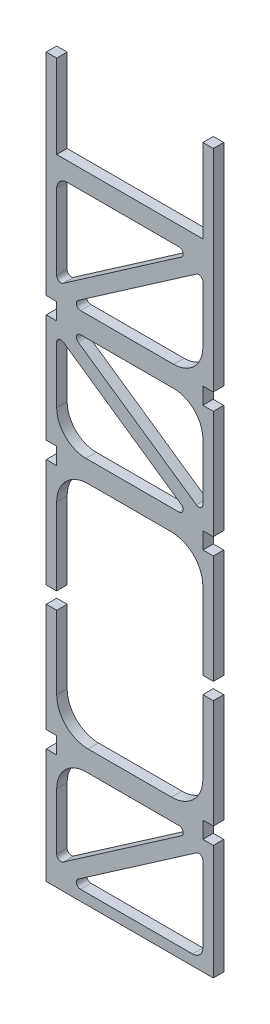
SolidWorks part; units mm, degrees
material "Balsa"
ref_plane "Front Plane" through (0, 0, 0) normal (0, 0, 1) x (1, 0, 0)
ref_plane "Top Plane" through (0, 0, 0) normal (0, 1, 0) x (1, 0, 0)
ref_plane "Right Plane" through (0, 0, 0) normal (1, 0, 0) x (0, 0, -1)
sketch "Model" plane through (0, 0, 0) normal (0, 0, 1) x (1, 0, 0)
  line L0 (-80.7688, 311.15) -> (-24.13, 311.15)
  line L1 (-10.3358, 365.5406) -> (-82.2146, 315.7784)
  line L2 (-6.35, 328.93) -> (-6.35, 363.4522)
  line L3 (-95.25, 287.2522) -> (-95.25, 252.73)
  line L4 (-19.3854, 239.5784) -> (-91.2642, 289.3406)
  line L5 (-77.47, 234.95) -> (-20.8312, 234.95)
  line L6 (-80.7688, 158.75) -> (-12.7, 158.75)
  line L7 (-10.3358, 213.1406) -> (-82.2146, 163.3784)
  line L8 (-6.35, 165.1) -> (-6.35, 211.0522)
  line L9 (-20.8312, 222.25) -> (-88.9, 222.25)
  line L10 (-91.2642, 167.8594) -> (-19.3854, 217.6216)
  line L11 (-95.25, 215.9) -> (-95.25, 169.9478)
  line L12 (-82.2146, 293.8216) -> (-10.3358, 244.0594)
  line L13 (-24.13, 298.45) -> (-80.7688, 298.45)
  line L14 (-6.35, 246.1478) -> (-6.35, 280.67)
  line L15 (-95.25, 134.8522) -> (-95.25, 88.9)
  line L16 (-19.3854, 87.1784) -> (-91.2642, 136.9406)
  line L17 (-88.9, 82.55) -> (-20.8312, 82.55)
  line L18 (-80.7688, 6.35) -> (-12.7, 6.35)
  line L19 (-10.3358, 60.7406) -> (-82.2146, 10.9784)
  line L20 (-6.35, 12.7) -> (-6.35, 58.6522)
  line L21 (-20.8312, 69.85) -> (-77.47, 69.85)
  line L22 (-91.2642, 15.4594) -> (-19.3854, 65.2216)
  line L23 (-95.25, 52.07) -> (-95.25, 17.5478)
  line L24 (-20.8312, 374.65) -> (-88.9, 374.65)
  line L25 (-91.2642, 320.2594) -> (-19.3854, 370.0216)
  line L26 (-95.25, 368.3) -> (-95.25, 322.3478)
  line L27 (-82.2146, 141.4216) -> (-10.3358, 91.6594)
  line L28 (-12.7, 146.05) -> (-80.7688, 146.05)
  line L29 (-6.35, 93.7478) -> (-6.35, 139.7)
  line L30 (-95.25, 386.08) -> (-6.35, 386.08)
  line L31 (-95.25, 386.08) -> (-95.25, 436.88)
  line L32 (-101.6, 436.88) -> (-95.25, 436.88)
  line L33 (-101.6, 0) -> (-101.6, 436.88)
  line L34 (-101.6, 0) -> (0, 0)
  line L35 (0, 0) -> (0, 436.88)
  line L36 (-6.35, 436.88) -> (0, 436.88)
  line L37 (-6.35, 386.08) -> (-6.35, 436.88)
  arc A0 (-77.47, 69.85) -> (-95.25, 52.07) centre (-77.47, 52.07) ccw
  arc A1 (-82.2146, 315.7784) -> (-80.7688, 311.15) centre (-80.7688, 313.69) ccw
  arc A2 (-6.35, 363.4522) -> (-10.3358, 365.5406) centre (-8.89, 363.4522) ccw
  arc A3 (-6.35, 328.93) -> (-24.13, 311.15) centre (-24.13, 328.93) cw
  arc A4 (-91.2642, 289.3406) -> (-95.25, 287.2522) centre (-92.71, 287.2522) ccw
  arc A5 (-20.8312, 234.95) -> (-19.3854, 239.5784) centre (-20.8312, 237.49) ccw
  arc A6 (-12.7, 158.75) -> (-6.35, 165.1) centre (-12.7, 165.1) ccw
  arc A7 (-82.2146, 163.3784) -> (-80.7688, 158.75) centre (-80.7688, 161.29) ccw
  arc A8 (-6.35, 211.0522) -> (-10.3358, 213.1406) centre (-8.89, 211.0522) ccw
  arc A9 (-88.9, 222.25) -> (-95.25, 215.9) centre (-88.9, 215.9) ccw
  arc A10 (-19.3854, 217.6216) -> (-20.8312, 222.25) centre (-20.8312, 219.71) ccw
  arc A11 (-95.25, 169.9478) -> (-91.2642, 167.8594) centre (-92.71, 169.9478) ccw
  arc A12 (-10.3358, 244.0594) -> (-6.35, 246.1478) centre (-8.89, 246.1478) ccw
  arc A13 (-80.7688, 298.45) -> (-82.2146, 293.8216) centre (-80.7688, 295.91) ccw
  arc A14 (-6.35, 280.67) -> (-24.13, 298.45) centre (-24.13, 280.67) ccw
  arc A15 (-95.25, 88.9) -> (-88.9, 82.55) centre (-88.9, 88.9) ccw
  arc A16 (-91.2642, 136.9406) -> (-95.25, 134.8522) centre (-92.71, 134.8522) ccw
  arc A17 (-20.8312, 82.55) -> (-19.3854, 87.1784) centre (-20.8312, 85.09) ccw
  arc A18 (-12.7, 6.35) -> (-6.35, 12.7) centre (-12.7, 12.7) ccw
  arc A19 (-82.2146, 10.9784) -> (-80.7688, 6.35) centre (-80.7688, 8.89) ccw
  arc A20 (-6.35, 58.6522) -> (-10.3358, 60.7406) centre (-8.89, 58.6522) ccw
  arc A21 (-77.47, 234.95) -> (-95.25, 252.73) centre (-77.47, 252.73) cw
  arc A22 (-19.3854, 65.2216) -> (-20.8312, 69.85) centre (-20.8312, 67.31) ccw
  arc A23 (-95.25, 17.5478) -> (-91.2642, 15.4594) centre (-92.71, 17.5478) ccw
  arc A24 (-88.9, 374.65) -> (-95.25, 368.3) centre (-88.9, 368.3) ccw
  arc A25 (-19.3854, 370.0216) -> (-20.8312, 374.65) centre (-20.8312, 372.11) ccw
  arc A26 (-95.25, 322.3478) -> (-91.2642, 320.2594) centre (-92.71, 322.3478) ccw
  arc A27 (-10.3358, 91.6594) -> (-6.35, 93.7478) centre (-8.89, 93.7478) ccw
  arc A28 (-80.7688, 146.05) -> (-82.2146, 141.4216) centre (-80.7688, 143.51) ccw
  arc A29 (-6.35, 139.7) -> (-12.7, 146.05) centre (-12.7, 139.7) ccw
  dimension "D1" = 17.78
  dimension "D2" = 17.78
extrude "Boss-Extrude1" add sketch "Model" along normal blind 6.35 contours L37 L30 L31 L32 L33 L34 L35 L36 A29 L29 A27 L27 A28 L28 A26 L26 A24 L24 A25 L25 A23 L23 L21 A22 L22 A20 L20 A18 L18 A19 L19 A17 L17 A15 L15 A16 L16 L14 A12 L12 A13 L13 | L11 A11 L10 A10 L9 A9 | L8 A8 L7 A7 L6 A6 | L29 A29 L28 A28 L27 A27 | L17 A17 L16 A16 L15 A15 region at (-33.751, 177.8784, 0) region at (-67.849, 203.1216, 0) region at (-67.849, 101.6784, 0) region at (-33.751, 126.9216, 0) region at (-50.8, 381.5946, 0)
sketch "Sketch1" plane through (0, 0, 6.35) normal (0, 0, 1) x (1, 0, 0)
  line L10 (-77.47, 234.95) -> (-20.8312, 234.95) construction
  line L11 (-76.2, 222.25) -> (-25.4, 222.25)
  line L12 (-95.25, 203.2) -> (-95.25, 101.6)
  line L13 (-76.2, 82.55) -> (-25.4, 82.55)
  line L14 (-6.35, 203.2) -> (-6.35, 101.6)
  line L15 (-20.8312, 69.85) -> (-77.47, 69.85) construction
  line L16 (-101.6, 0) -> (-101.6, 436.88) construction
  line L17 (0, 0) -> (0, 436.88) construction
  arc A4 (-25.4, 82.55) -> (-6.35, 101.6) centre (-25.4, 101.6) ccw
  arc A5 (-25.4, 222.25) -> (-6.35, 203.2) centre (-25.4, 203.2) cw
  arc A6 (-76.2, 222.25) -> (-95.25, 203.2) centre (-76.2, 203.2) ccw
  arc A7 (-95.25, 101.6) -> (-76.2, 82.55) centre (-76.2, 101.6) ccw
  dimension "D2" = 12.7
  dimension "D5" = 19.05
  dimension "D1" = 12.7
  dimension "D3" = 6.35
  dimension "D4" = 6.35
extrude "Cut-Extrude1" cut sketch "Sketch1" against normal up to surface (6.35 mm away) contours L12 A7 L13 A4 L14 A5 L11 A6 region at (-50.8, 152.4, 6.35) up to face at (-68.521, 355.145, 0)
sketch "Sketch2" plane through (0, 0, 6.35) normal (0, 0, 1) x (1, 0, 0)
  line L0 (-101.6, 0) -> (-101.6, 436.88) construction
  line L4 (-95.25, 69.85) -> (-101.6, 69.85)
  line L24 (-50.8, 0) -> (-50.8, 386.08) construction
  line L43 (-95.25, 69.85) -> (-95.25, 80.01)
  line L44 (-95.25, 80.01) -> (-101.6, 80.01)
  line L45 (-101.6, 69.85) -> (-101.6, 80.01)
  line L46 (-95.25, 203.2) -> (-95.25, 101.6) construction
  line L47 (-95.25, 146.05) -> (-101.6, 146.05)
  line L48 (-95.25, 146.05) -> (-95.25, 156.21)
  line L49 (-95.25, 156.21) -> (-101.6, 156.21)
  line L50 (-101.6, 146.05) -> (-101.6, 156.21)
  line L51 (-20.8312, 69.85) -> (-77.47, 69.85) construction
  line L52 (-95.25, 222.25) -> (-101.6, 222.25)
  line L53 (-95.25, 222.25) -> (-95.25, 232.41)
  line L54 (-95.25, 232.41) -> (-101.6, 232.41)
  line L55 (-101.6, 222.25) -> (-101.6, 232.41)
  line L56 (-95.25, 298.45) -> (-101.6, 298.45)
  line L57 (-95.25, 298.45) -> (-95.25, 308.61)
  line L58 (-95.25, 308.61) -> (-101.6, 308.61)
  line L59 (-101.6, 298.45) -> (-101.6, 308.61)
  line L60 (-95.25, 287.2522) -> (-95.25, 252.73) construction
  line L61 (-76.2, 222.25) -> (-25.4, 222.25) construction
  line L62 (-24.13, 298.45) -> (-80.7688, 298.45) construction
  line L63 (-6.35, 308.61) -> (0, 308.61)
  line L64 (0, 298.45) -> (0, 308.61)
  line L65 (-6.35, 298.45) -> (0, 298.45)
  line L66 (-6.35, 298.45) -> (-6.35, 308.61)
  line L67 (-6.35, 232.41) -> (0, 232.41)
  line L68 (0, 222.25) -> (0, 232.41)
  line L69 (-6.35, 222.25) -> (0, 222.25)
  line L70 (-6.35, 222.25) -> (-6.35, 232.41)
  line L71 (-6.35, 156.21) -> (0, 156.21)
  line L72 (0, 146.05) -> (0, 156.21)
  line L73 (-6.35, 146.05) -> (0, 146.05)
  line L74 (-6.35, 146.05) -> (-6.35, 156.21)
  line L75 (-6.35, 80.01) -> (0, 80.01)
  line L76 (0, 69.85) -> (0, 80.01)
  line L77 (-6.35, 69.85) -> (0, 69.85)
  line L78 (-6.35, 69.85) -> (-6.35, 80.01)
  line L79 (-101.6, 0) -> (0, 0) construction
  line L80 (-95.25, 386.08) -> (-6.35, 386.08) construction
  point P34 (-50.8, 0)
  point P36 (-50.8, 381.0884)
  point P37 (-50.8, 386.08)
  point P50 (-50.8, 0)
  point P52 (0, 0)
  dimension "D1" = 10.16
  dimension "D2" = 66.04
extrude "Cut-Extrude2" cut sketch "Sketch2" against normal up to surface (6.35 mm away) contours L74 L73 L72 L71 | L70 L69 L68 L67 | L58 L59 L56 L57 | L55 L54 L53 L52 | L48 L49 L50 L47 | L4 L45 L44 L43 | L78 L75 L76 L77 | L66 L63 L64 L65 region at (-3.175, 227.33, 6.35) region at (-3.175, 151.13, 6.35) up to face at (-50.8, 152.4, 0)
equation "\"thick\"=0.25"
equation "\"D1@Boss-Extrude1\"=\"thick\""
